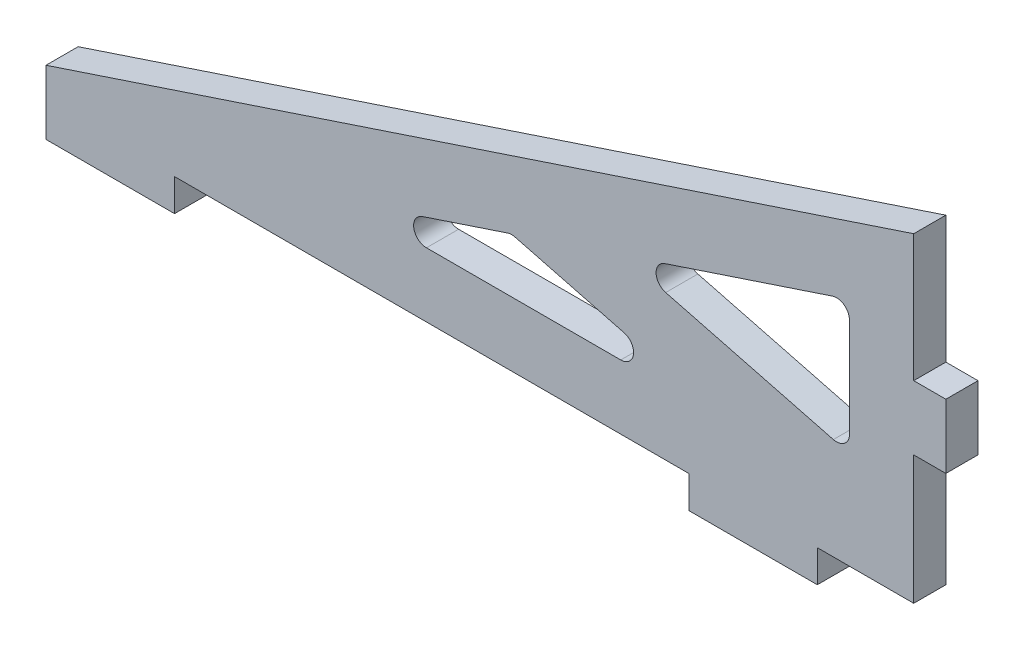
SolidWorks part; units mm, degrees
ref_plane "Front Plane" through (0, 0, 0) normal (0, 0, 1) x (1, 0, 0)
ref_plane "Top Plane" through (0, 0, 0) normal (0, 1, 0) x (1, 0, 0)
ref_plane "Right Plane" through (0, 0, 0) normal (1, 0, 0) x (0, 0, -1)
sketch "Sketch2" plane through (0, 0, 0) normal (0, 0, 1) x (1, 0, 0)
  line L0 (-92.95, 148.308) -> (78.5, 205.204)
  line L1 (78.5, 205.204) -> (84.85, 205.204) construction
  line L2 (84.85, 205.204) -> (84.85, 180.058) construction
  line L4 (-118.35, 135.608) -> (-118.35, 141.958) construction
  line L5 (84.85, 167.358) -> (84.85, 141.958) construction
  line L6 (84.85, 180.058) -> (78.5, 180.058)
  line L8 (84.85, 167.358) -> (78.5, 167.358)
  line L9 (78.5, 180.058) -> (78.5, 167.358) construction
  line L10 (-92.95, 135.608) -> (-92.95, 148.308) construction
  line L13 (-67.55, 141.958) -> (-67.55, 135.608)
  line L15 (34.05, 135.608) -> (34.05, 141.958)
  line L17 (59.45, 141.958) -> (59.45, 135.608)
  line L19 (-92.95, 135.608) -> (-118.35, 135.608) construction
  line L20 (-92.95, 141.958) -> (-92.95, 135.608)
  line L21 (-92.95, 141.958) -> (-92.95, 148.308)
  line L22 (-92.95, 135.608) -> (-67.55, 135.608)
  line L23 (-67.55, 141.958) -> (34.05, 141.958)
  line L24 (34.05, 135.608) -> (59.45, 135.608)
  line L25 (59.45, 141.958) -> (78.5, 141.958)
  line L26 (78.5, 167.358) -> (78.5, 141.958)
  line L27 (84.85, 167.358) -> (84.85, 180.058)
  line L28 (78.5, 180.058) -> (78.5, 205.204)
  point P6 (203.2, 5.8305)
  point P22 (-118.35, 141.958)
  dimension "D1" = 6.35
  dimension "D2" = 6.35
  dimension "D3" = 6.35
  dimension "D4" = 12.7
  dimension "D5" = 6.35
  dimension "D6" = 25.4
  dimension "D7" = 25.4
  dimension "D8" = 25.4
  dimension "D9" = 25.4
  dimension "D10" = 6.35
  dimension "D11" = 25.4
extrude "Boss-Extrude1" add sketch "Sketch2" along normal blind 6.35
sketch "Sketch3" plane through (0, 0, 6.35) normal (0, 0, 1) x (1, 0, 0)
  line L0 (-33.4926, 154.658) -> (65.8, 187.6084)
  line L1 (65.8, 187.6084) -> (65.8, 154.658)
  line L2 (65.8, 154.658) -> (-33.4926, 154.658)
  line L3 (78.5, 205.204) -> (-92.95, 148.308) construction
  line L4 (-67.55, 141.958) -> (34.05, 141.958) construction
  line L6 (65.8, 154.658) -> (-19.3713, 176.756) construction
  line L7 (64.2053, 148.5115) -> (-20.9661, 170.6095)
  line L8 (67.3947, 160.8045) -> (-17.7766, 182.9025)
  line L9 (78.5, 180.058) -> (78.5, 205.204) construction
  arc A0 (64.2053, 148.5115) -> (67.3947, 160.8045) centre (65.8, 154.658) ccw
  arc A1 (-17.7766, 182.9025) -> (-20.9661, 170.6095) centre (-19.3713, 176.756) ccw
  point P10 (23.2143, 165.707)
  point P15 (122.5424, 38.8398)
  point P16 (124.2169, 40.634)
  point P17 (154.5054, 110.6588)
  point P18 (0, 0)
  point P19 (-19.3713, 176.756)
  dimension "D4" = 6.35
  dimension "D1" = 12.7
  dimension "D2" = 12.7
  dimension "D3" = 12.7
extrude "Cut-Extrude1" cut sketch "Sketch3" against normal through all contours L2 L7 L0 | L8 L1 L0 region at (2.001, 158.2501, 6.35) region at (50.9232, 173.8748, 6.35)
fillet "Fillet1" radius 2.54 6 edges at (65.8, 187.6084, 3.175) (21.1696, 172.7978, 3.175) (-1.0194, 165.4343, 3.175) (40.5151, 154.658, 3.175) (-33.4926, 154.658, 3.175) (65.8, 161.2182, 3.175)
